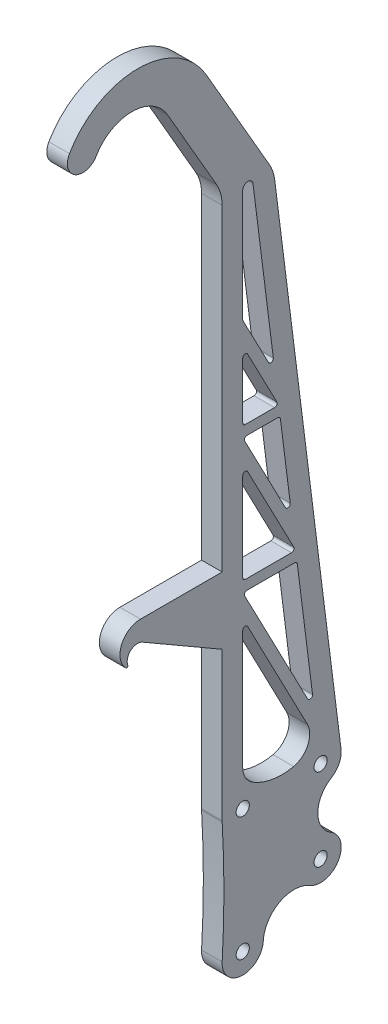
SolidWorks part; units mm, degrees
ref_plane "Front Plane" through (0, 0, 0) normal (0, 0, 1) x (1, 0, 0)
ref_plane "Top Plane" through (0, 0, 0) normal (0, 1, 0) x (1, 0, 0)
ref_plane "Right Plane" through (0, 0, 0) normal (1, 0, 0) x (0, 0, -1)
sketch "Sketch1" plane through (0, 0, 0) normal (1, 0, 0) x (0, 0, -1)
  line L1 (12.0015, 19.05) -> (12.0015, -6.35) construction
  line L2 (-12.0015, -19.05) -> (-12.0015, 19.05) construction
  line L3 (12.0015, 0) -> (-12.0015, 0) construction
  line L4 (-6.35, 19.05) -> (6.35, 19.05) construction
  line L5 (-18.3515, 19.05) -> (-18.3515, 183.3563)
  line L6 (8.7396, -11.7982) -> (-4.7505, -3.7215) construction
  line L7 (18.3016, 19.8442) -> (-2.4765, 184.6629)
  line L8 (-12.0015, 25.4) -> (-12.0015, 69.85)
  line L9 (-57.173, 215.9) -> (-72.296, 189.7062) construction
  line L10 (-61.2974, 170.6563) -> (-31.0515, 170.6563) construction
  line L11 (-20.053, 189.7062) -> (-35.1759, 215.9)
  line L12 (-46.1745, 209.55) -> (-61.2974, 183.3562) construction
  line L13 (-61.2974, 183.3562) -> (-31.0515, 183.3562) construction
  line L14 (-31.0515, 183.3562) -> (-46.1745, 209.55) construction
  line L15 (-23.2609, 220.6625) -> (-2.4765, 184.6629)
  line L16 (-2.4765, 184.6629) -> (-13.475, 178.3129) construction
  line L17 (-57.173, 215.9) -> (-65.4219, 220.6625) construction
  line L18 (15.2634, -0.9018) -> (7.7798, 3.5787) construction
  line L19 (-12.0015, 69.85) -> (11.2073, 25.3501)
  line L20 (11.2073, 25.3501) -> (-0.8823, 121.2482) construction
  line L21 (8.7396, 24.4982) -> (1.1915, 19.979) construction
  line L22 (15.2634, 13.6018) -> (8.3747, 9.4775) construction
  line L23 (10.0658, 34.4046) -> (-12.0015, 76.7159)
  line L24 (-12.0015, 76.7159) -> (4.7318, 76.7159)
  line L25 (4.7318, 76.7159) -> (10.0658, 34.4046)
  line L26 (4.3315, 79.8909) -> (-12.0015, 79.8909)
  line L27 (-12.0015, 79.8909) -> (-12.0015, 111.2073)
  line L28 (-12.0015, 111.2073) -> (4.3315, 79.8909)
  line L29 (3.19, 88.9454) -> (-12.0015, 118.0732)
  line L30 (-12.0015, 118.0732) -> (-0.482, 118.0732)
  line L31 (-0.482, 118.0732) -> (3.19, 88.9454)
  line L32 (-0.8823, 121.2482) -> (-12.0015, 121.2482)
  line L33 (-12.0015, 121.2482) -> (-12.0015, 142.5679)
  line L34 (-8.839, 184.3631) -> (-2.0238, 130.3027)
  line L35 (-12.0015, 69.85) -> (-9.1864, 71.3182) construction
  line L36 (-12.0015, 76.7159) -> (-12.0015, 79.8909) construction
  line L37 (-12.0015, 111.2073) -> (-9.1864, 112.6755) construction
  line L38 (-12.0015, 118.0732) -> (-12.0015, 121.2482) construction
  line L39 (-0.8823, 121.2482) -> (-12.0015, 142.5679)
  line L40 (-2.0238, 130.3027) -> (-12.0015, 149.4338)
  line L41 (-12.0015, 142.5679) -> (-9.1864, 144.0361) construction
  line L42 (-2.0238, 130.3027) -> (-1.5228, 126.3291) construction
  line L43 (-12.0015, 149.4338) -> (-12.0015, 184.1645)
  line L44 (-18.3408, -18.6818) -> (-16.9094, 5.9637) construction
  line L45 (-5.6622, -19.4182) -> (-4.7505, -3.7215) construction
  circle A0 centre (-12.0015, 19.05) radius 5.6515 construction
  circle A1 centre (12.0015, 19.05) radius 5.6515 construction
  arc A2 (-18.3408, -18.6818) -> (-5.6622, -19.4182) centre (-12.0015, -19.05) ccw
  arc A3 (8.7396, -11.7982) -> (15.2634, -0.9018) centre (12.0015, -6.35) ccw
  arc A4 (15.2634, 13.6018) -> (18.3016, 19.8442) centre (12.0015, 19.05) ccw
  arc A5 (15.2634, 13.6018) -> (15.2634, -0.9018) centre (19.6051, 6.35) ccw
  arc A7 (-35.1759, 215.9) -> (-57.173, 215.9) centre (-46.1745, 209.55) ccw
  arc A8 (-72.296, 189.7062) -> (-61.2974, 170.6563) centre (-61.2974, 183.3562) ccw construction
  arc A9 (-31.0515, 170.6563) -> (-20.053, 189.7062) centre (-31.0515, 183.3562) ccw construction
  circle A10 centre (-46.1745, 192.0875) radius 8.7312 construction
  arc A11 (-18.3515, 183.3563) -> (-20.053, 189.7062) centre (-31.0515, 183.3563) ccw
  arc A12 (-57.173, 215.9) -> (-65.4219, 220.6625) centre (-61.2974, 218.2813) cw
  arc A13 (-65.4219, 220.6625) -> (-23.2609, 220.6625) centre (-44.3414, 208.4917) cw
  arc A14 (-5.6622, -19.4182) -> (8.7396, -11.7982) centre (3.8468, -19.9704) cw
  arc A15 (-12.0015, 25.4) -> (-8.7396, 24.4982) centre (-12.0015, 19.05) cw
  arc A17 (11.2073, 25.3501) -> (8.7396, 24.4982) centre (12.0015, 19.05) ccw
  arc A18 (8.7396, 24.4982) -> (-8.7396, 24.4982) centre (0, 39.0956) cw
  arc A19 (-12.0015, 184.1645) -> (-8.839, 184.3631) centre (-10.414, 184.1645) cw
  arc A20 (-18.3515, 19.05) -> (-18.3408, 18.6818) centre (-12.0015, 19.05) ccw
  arc A21 (-18.3408, -18.6818) -> (-18.3408, 18.6818) centre (-340.0076, 0) ccw
  point P11 (0, 0)
  point P47 (-12.0015, 0)
  point P48 (-46.1745, 222.25)
  dimension "D3" = 12.7
  dimension "D4" = 11.303
  dimension "D5" = 6.35
  dimension "D6" = 15.875
  dimension "D7" = 12.7
  dimension "D9" = 12.7
  dimension "D10" = 4.7625
  dimension "D12" = 6.35
  dimension "D14" = 3.175
  dimension "D15" = 1.5875
  dimension "D17" = 9.525
  dimension "D1" = 25.4
  dimension "D2" = 38.1
  dimension "D8" = 38.8937
  dimension "D11" = 222.25
  dimension "D13" = 6.35
  dimension "D16" = 44.45
extrude "Boss-Extrude1" add sketch "Sketch1" along normal mid plane 6.35
sketch "Sketch2" plane through (3.175, 0, 0) normal (1, 0, 0) x (0, 0, -1)
  line L0 (-12.0015, -19.05) -> (-12.0015, 19.05) construction
  circle A0 centre (12.0015, -6.35) radius 2.032
  circle A1 centre (12.0015, 19.05) radius 2.032
  circle A2 centre (-12.0015, 19.05) radius 2.032
  circle A3 centre (-12.0015, -19.05) radius 2.032
  dimension "D1" = 4.064
extrude "Cut-Extrude1" cut sketch "Sketch2" against normal through all
fillet "Fillet1" radius 12.7 1 edges at (0, 184.6629, 2.4765)
fillet "Fillet2" radius 0.7937 15 edges at (0, 121.2482, 12.0015) (0, 118.0732, 12.0015) (0, 118.0732, 0.482) (0, 88.9454, -3.19) (0, 111.2073, 12.0015) (0, 79.8909, 12.0015) (0, 79.8909, -4.3315) (0, 69.85, 12.0015) (0, 76.7159, 12.0015) (0, 76.7159, -4.7318) (0, 34.4046, -10.0658) (0, 149.4338, 12.0015) (0, 121.2482, 0.8823) (0, 142.5679, 12.0015) (0, 130.3027, 2.0238)
fillet "Fillet3" radius 6.35 2 edges at (0, 25.4, 12.0015) (0, 25.3501, -11.2073)
sketch "Sketch3" plane through (3.175, 0, 0) normal (1, 0, 0) x (0, 0, -1)
  line L1 (-18.3515, 183.3563) -> (-18.3515, 19.05) construction
  line L2 (-18.3515, 85.4357) -> (-18.3515, 64.7982)
  line L4 (-18.3515, 85.4357) -> (-43.5091, 85.4357)
  line L5 (-42.8625, 78.9496) -> (-18.3515, 64.7982)
  line L6 (-18.3515, 64.7982) -> (-18.3515, 85.4357)
  arc A0 (-42.8625, 78.9496) -> (-47.4269, 75.0962) centre (-44.45, 76.2) ccw
  arc A1 (-43.5091, 85.4357) -> (-48.0851, 74.683) centre (-43.5091, 79.0857) ccw
  arc A2 (-48.0851, 74.683) -> (-47.4269, 75.0962) centre (-47.7991, 74.9582) ccw
  point P2 (-18.3515, 64.4244)
  point P3 (-42.8625, 83.4653)
  point P11 (-48.2403, 75.8777)
  point P12 (-48.2116, 76.7043)
  point P14 (-42.5451, 75.8997)
  dimension "D1" = 3.175
  dimension "D2" = 76.2
  dimension "D4" = 6.35
  dimension "D5" = 0.3969
  dimension "D3" = 44.45
  dimension "D6" = 60
  dimension ".475" = 10.16
  dimension "D8" = 20.6375
extrude "Boss-Extrude2" add sketch "Sketch3" against normal up to surface (6.35 mm away) contours A1 A2 A0 L5 L2 L4 region at (3.175, 78.383, 30.5834) up to face at (-3.175, -19.05, 9.9695)
